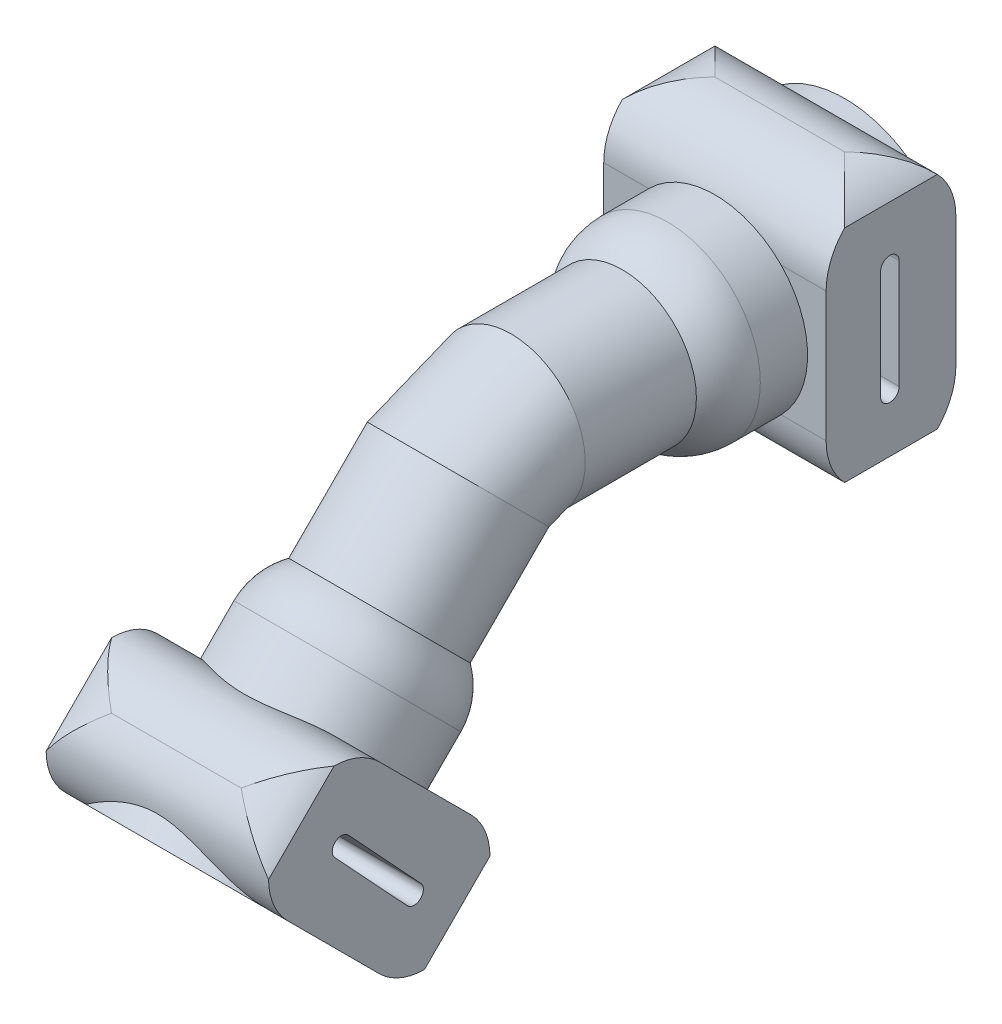
SolidWorks part; units mm, degrees
material "CA"
ref_plane "Front" through (0, 0, 0) normal (0, 0, 1) x (1, 0, 0)
ref_plane "Top" through (0, 0, 0) normal (0, 1, 0) x (1, 0, 0)
ref_plane "Right" through (0, 0, 0) normal (1, 0, 0) x (0, 0, -1)
sketch "Sketch1" plane through (0, 0, 0) normal (0, 0, 1) x (1, 0, 0)
  line L1 (-7, -7) -> (7, -7)
  line L2 (-7, -7) -> (-7, 7)
  line L3 (-7, 7) -> (7, 7)
  line L4 (7, -7) -> (7, 7)
  line L5 (-7, -7) -> (7, 7) construction
  line L6 (-7, 7) -> (7, -7) construction
  point P0 (0, 0)
extrude "Boss-Extrude1" add sketch "Sketch1" along normal blind 7
fillet "Fillet1" radius 3.5 8 edges at (-7, -7, 3.5) (0, -7, 7) (7, -7, 3.5) (0, -7, 0) (7, 7, 3.5) (0, 7, 7) (-7, 7, 3.5) (0, 7, 0)
sketch "Sketch2" plane through (0, 0, 0) normal (0, 0, -1) x (-1, 0, 0)
  circle A0 centre (0, 0) radius 6
extrude "Boss-Extrude2" add sketch "Sketch2" against normal blind 5
sketch "Sketch3" plane through (0, 0, 0) normal (0, 0, -1) x (-1, 0, 0)
  circle A0 centre (0, 0) radius 3
extrude "Cut-Extrude1" cut sketch "Sketch3" against normal blind 5
sketch "Sketch4" plane through (7, 0, 0) normal (1, 0, 0) x (0, 0, -1)
  line L0 (-3.5613, 2.947) -> (-3.5613, -2.9279) construction
  line L1 (-3.0613, 2.947) -> (-3.0613, -2.9279)
  line L2 (-4.0613, 2.947) -> (-4.0613, -2.9279)
  arc A0 (-3.0613, 2.947) -> (-4.0613, 2.947) centre (-3.5613, 2.947) ccw
  arc A1 (-4.0613, -2.9279) -> (-3.0613, -2.9279) centre (-3.5613, -2.9279) ccw
  point P2 (-3.5613, 0.0095)
extrude "Cut-Extrude2" cut sketch "Sketch4" against normal blind 35
ref_plane "Plane1" through (6, 0, 0) normal (1, 0, 0) x (0, 0, -1)
sketch "Sketch5" plane through (6, 0, 0) normal (1, 0, 0) x (0, 0, -1)
  line L1 (-19.4309, 23.2922) -> (3.0331, 23.2922)
  line L2 (-19.4309, 23.2922) -> (-19.4309, -8.3854)
  line L3 (-19.4309, -8.3854) -> (3.0331, -8.3854)
  line L4 (3.0331, 23.2922) -> (3.0331, -8.3854)
  line L5 (-19.4309, 23.2922) -> (3.0331, -8.3854) construction
  line L6 (-19.4309, -8.3854) -> (3.0331, 23.2922) construction
  point P0 (-8.1989, 7.4534)
extrude "Cut-Extrude3" cut sketch "Sketch5" along normal blind 17
mirror "Mirror1" about plane through (0, 0, 0) normal (1, 0, 0) of "Cut-Extrude3"
sketch "Sketch6" plane through (0, 0, 7) normal (0, 0, 1) x (1, 0, 0)
  circle A0 centre (0, 0) radius 5
extrude "Boss-Extrude3" add sketch "Sketch6" along normal blind 5
sketch "Sketch7" plane through (0, 0, 12) normal (0, 0, 1) x (1, 0, 0)
  circle A0 centre (0, 0) radius 4
extrude "Boss-Extrude4" add sketch "Sketch7" along normal blind 6
fillet "Fillet2" radius 3.5 1 edges at (5, 0, 12)
sketch "Sketch8" plane through (0, 0, 5) normal (0, 0, -1) x (-1, 0, 0)
  circle A0 centre (0, 0) radius 2
extrude "Cut-Extrude4" cut sketch "Sketch8" against normal blind 6
ref_plane "Plane2" through (0, 0, 18) normal (0, 0, 1) x (1, 0, 0)
ref_plane "Plane3" through (0, -4, 0) normal (0, 1, 0) x (1, 0, 0)
ref_plane "Plane4" through (0, -11, 11) normal (0, 0.7071, -0.7071) x (-1, 0, 0)
sketch "Sketch9" plane through (0, -11, 11) normal (0, 0.7071, -0.7071) x (-1, 0, 0)
  circle A0 centre (0, 13.941) radius 4
extrude "Boss-Extrude5" add sketch "Sketch9" against normal blind 6 separate body contours A0
loft "Loft1" add section edge at (4, 0, 18) section face at (0, 1.6862, 23.6862) connector at (0.9717, 3.8802, 18) connector at (0.9229, 1.6099, 23.6099)
sketch "Sketch10" plane through (0, -15.2426, 15.2426) normal (0, -0.7071, 0.7071) x (1, 0, 0)
  circle A0 centre (0, 13.941) radius 5
extrude "Boss-Extrude6" add sketch "Sketch10" along normal blind 5 contours A0
fillet "Fillet3" radius 3.5 1 edges at (0, -8.9204, 21.5649)
sketch "Sketch11" plane through (0, -18.7782, 18.7782) normal (0, -0.7071, 0.7071) x (1, 0, 0)
  line L1 (-7, 6.941) -> (7, 6.941)
  line L2 (-7, 6.941) -> (-7, 20.941)
  line L3 (-7, 20.941) -> (7, 20.941)
  line L4 (7, 6.941) -> (7, 20.941)
  line L5 (-7, 6.941) -> (7, 20.941) construction
  line L6 (-7, 20.941) -> (7, 6.941) construction
  point P0 (0, 13.941)
extrude "Boss-Extrude7" add sketch "Sketch11" along normal blind 7 contours L1 L4 L3 L2
fillet "Fillet4" radius 3.5 8 edges at (-7, -16.345, 26.1611) (0, -18.8199, 28.6359) (7, -16.345, 26.1611) (0, -13.8702, 23.6862) (7, -6.4455, 36.0606) (0, -8.9204, 38.5354) (-7, -6.4455, 36.0606) (0, -3.9707, 33.5857)
sketch "Sketch12" plane through (0, -23.7279, 23.7279) normal (0, -0.7071, 0.7071) x (1, 0, 0)
  circle A0 centre (0, 13.941) radius 6
extrude "Boss-Extrude8" add sketch "Sketch12" against normal blind 5
sketch "Sketch13" plane through (0, -23.7279, 23.7279) normal (0, -0.7071, 0.7071) x (1, 0, 0)
  circle A0 centre (0, 13.941) radius 3
extrude "Cut-Extrude5" cut sketch "Sketch13" against normal blind 5
sketch "Sketch14" plane through (-7, 0, 0) normal (-1, 0, 0) x (0, 0, 1)
  line L0 (29.2302, -13.5884) -> (33.149, -9.3724) construction
  line L1 (28.864, -13.248) -> (32.7828, -9.032)
  line L2 (29.5964, -13.9288) -> (33.5153, -9.7128)
  arc A0 (28.864, -13.248) -> (29.5964, -13.9288) centre (29.2302, -13.5884) ccw
  arc A1 (33.5153, -9.7128) -> (32.7828, -9.032) centre (33.149, -9.3724) ccw
  point P2 (31.1896, -11.4804)
extrude "Cut-Extrude6" cut sketch "Sketch14" against normal blind 20
sketch "Sketch15" plane through (6, 0, 0) normal (1, 0, 0) x (0, 0, -1)
  line L1 (-60.1681, 14.6354) -> (-19.3811, 14.6354)
  line L2 (-60.1681, 14.6354) -> (-60.1681, -22.8083)
  line L3 (-60.1681, -22.8083) -> (-19.3811, -22.8083)
  line L4 (-19.3811, 14.6354) -> (-19.3811, -22.8083)
  line L5 (-60.1681, 14.6354) -> (-19.3811, -22.8083) construction
  line L6 (-60.1681, -22.8083) -> (-19.3811, 14.6354) construction
  point P0 (-39.7746, -4.0865)
extrude "Cut-Extrude7" cut sketch "Sketch15" along normal blind 6
mirror "Mirror20" about plane through (0, 0, 0) normal (1, 0, 0) of "Cut-Extrude7"
sketch "Sketch16" plane through (0, -20.1924, 20.1924) normal (0, -0.7071, 0.7071) x (1, 0, 0)
  circle A0 centre (0, 13.941) radius 2
extrude "Cut-Extrude8" cut sketch "Sketch16" against normal blind 6 contours A0
